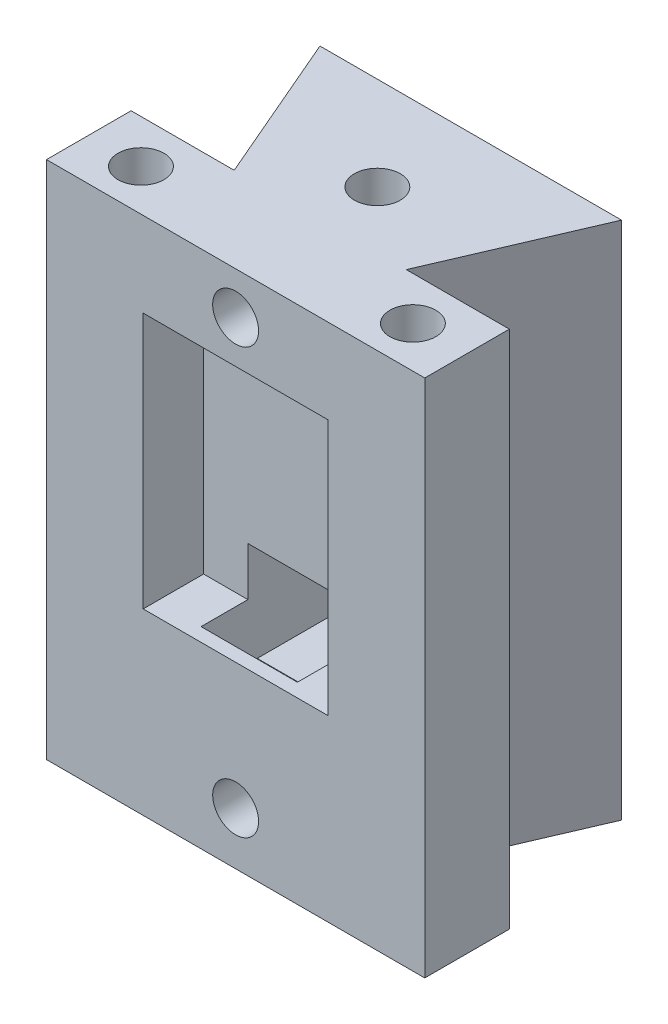
SolidWorks part; units mm, degrees
ref_plane "前视基准面" through (0, 0, 0) normal (0, 0, 1) x (1, 0, 0)
ref_plane "上视基准面" through (0, 0, 0) normal (0, 1, 0) x (1, 0, 0)
ref_plane "右视基准面" through (0, 0, 0) normal (1, 0, 0) x (0, 0, -1)
other "Configuration Table"
sketch "草图2" plane through (0, 0, 0) normal (0, 0, 1) x (1, 0, 0)
  line L1 (-7.65, 10.6) -> (7.65, 10.6)
  line L2 (-7.65, 10.6) -> (-7.65, -10.6)
  line L3 (-7.65, -10.6) -> (7.65, -10.6)
  line L4 (7.65, 10.6) -> (7.65, -10.6)
  line L5 (-7.65, 10.6) -> (7.65, -10.6) construction
  line L6 (-7.65, -10.6) -> (7.65, 10.6) construction
  line L9 (0, 0) -> (0, -50000) construction
  line L10 (-15.65, 17.6) -> (15.65, 17.6)
  line L11 (-15.65, 17.6) -> (-15.65, -16.6)
  line L12 (-15.65, -16.6) -> (15.65, -16.6)
  line L13 (15.65, 17.6) -> (15.65, -16.6)
  line L14 (0, 0) -> (50000, 0) construction
  point P0 (0, 0)
  dimension "D1" = 15.3
  dimension "D2" = 21.2
  dimension "D3" = 7
  dimension "D4" = 6
  dimension "D5" = 8
extrude "凸台-拉伸1" add sketch "草图2" along normal blind 7
extrude "凸台-拉伸2" add sketch "草图2<3>" along normal blind 2 contours L4 L1 L2 L3 region at (0, 0, 0)
sketch "草图2<3>" plane through (0, 0, 0) normal (0, 0, 1) x (1, 0, 0) same geometry as "草图2"
sketch "草图5" plane through (0, -10.6, 0) normal (0, 1, 0) x (1, 0, 0)
  line L0 (0, 0) -> (0, -14.0073) construction
  line L1 (-3.9855, -1.2239) -> (3.9855, -1.2239)
  line L2 (-3.9855, -1.2239) -> (-3.9855, -5.8726)
  line L3 (-3.9855, -5.8726) -> (3.9855, -5.8726)
  line L4 (3.9855, -1.2239) -> (3.9855, -5.8726)
extrude "切除-拉伸2" cut sketch "草图5" against normal blind 7
sketch "草图6" plane through (0, -16.6, 0) normal (0, -1, 0) x (1, 0, 0)
  line L0 (0, 0) -> (0, -12.7802) construction
  circle A0 centre (-11.25, 3.5834) radius 1.9
  circle A1 centre (11.25, 3.5834) radius 1.9
  dimension "D1" = 3.8
  dimension "D2" = 22.5
extrude "切除-拉伸3" cut sketch "草图6" against normal through all both and the other way through all
sketch "草图7" plane through (0, -16.6, 0) normal (0, -1, 0) x (1, 0, 0)
  line L0 (0, 0) -> (0, -14.4913) construction
  line L2 (-15.65, 0) -> (15.65, 0) construction
  line L4 (7.1187, 0) -> (-7.1187, 0)
  line L5 (-7.1187, 0) -> (-12.4765, -12.4538)
  line L6 (-12.4765, -12.4538) -> (12.4765, -12.4538)
  line L7 (12.4765, -12.4538) -> (7.1187, 0)
extrude "凸台-拉伸3" add sketch "草图7" against normal up to surface (34.2 mm away) up to face at (-9.35, 17.6, 3.5834)
sketch "草图8" plane through (0, 0, 7) normal (0, 0, 1) x (1, 0, 0)
  line L0 (0, 10.6) -> (0, -49989.4) construction
  line L1 (7.65, 10.6) -> (-7.65, 10.6) construction
  line L2 (-7.65, 10.6) -> (7.65, 10.6) construction
  circle A0 centre (0, 14.1) radius 1.9
  point P4 (0, 10.6)
  dimension "D1" = 3.8
  dimension "D2" = 3.5
extrude "切除-拉伸4" cut sketch "草图8" against normal blind 6
sketch "草图9" plane through (0, 0, 2) normal (0, 0, 1) x (1, 0, 0)
  line L0 (0, 0) -> (0, -21.8388) construction
  line L1 (-3.9855, -15.2007) -> (3.9855, -15.2007)
  line L2 (-3.9855, -15.2007) -> (-3.9855, -6.5767)
  line L3 (-3.9855, -6.5767) -> (3.9855, -6.5767)
  line L4 (3.9855, -15.2007) -> (3.9855, -6.5767)
  line L5 (-3.9855, -10.6) -> (-3.9855, -16.6) construction
extrude "切除-拉伸5" cut sketch "草图9" against normal through all
sketch "草图10" plane through (0, -16.6, 0) normal (0, -1, 0) x (1, 0, 0)
  line L0 (-15.65, 7) -> (-15.65, 0)
  line L1 (-15.65, 0) -> (-7.1187, 0)
  line L7 (7.1187, 0) -> (15.65, 0)
  line L8 (15.65, 0) -> (15.65, 7)
  line L10 (-7.1187, 0) -> (-12.4765, -12.4538)
  line L15 (12.4765, -12.4538) -> (7.1187, 0)
  line L16 (-15.65, 7) -> (15.65, 7) construction
  line L17 (-15.65, 7) -> (-15.65, 0) construction
  line L20 (15.65, 7) -> (15.65, 0) construction
  line L23 (-12.4765, -12.4538) -> (12.4765, -12.4538)
  line L24 (-15.65, 7) -> (15.65, 7)
  circle A0 centre (-11.25, 3.5834) radius 1.9
  circle A1 centre (11.25, 3.5834) radius 1.9
  dimension "D1" = 3.8
  dimension "D2" = 3.8
extrude "凸台-拉伸4" add sketch "草图10" along normal blind 8.8
sketch "草图11" plane through (0, 0, 7) normal (0, 0, 1) x (1, 0, 0)
  circle A0 centre (0, -21.0631) radius 1.9
  dimension "D1" = 3.8
extrude "切除-拉伸6" cut sketch "草图11" against normal blind 8 and the other way through all
sketch "草图12" plane through (0, -25.4, 0) normal (0, -1, 0) x (1, 0, 0)
  circle A0 centre (0, -4.7272) radius 1.9
  dimension "D1" = 3.8
extrude "切除-拉伸7" cut sketch "草图12" against normal through all both and the other way through all
